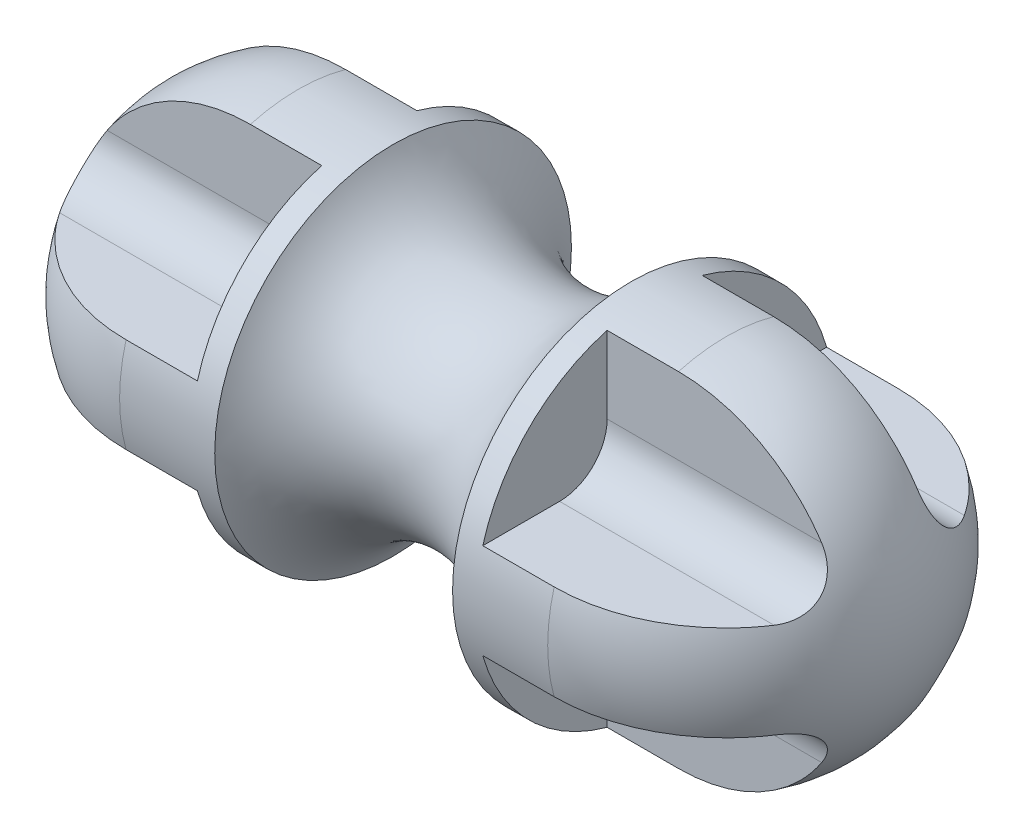
SolidWorks part; units mm, degrees
ref_plane "前视基准面" through (0, 0, 0) normal (0, 0, 1) x (1, 0, 0)
ref_plane "上视基准面" through (0, 0, 0) normal (0, 1, 0) x (1, 0, 0)
ref_plane "右视基准面" through (0, 0, 0) normal (1, 0, 0) x (0, 0, -1)
other "Configuration Table"
sketch "草图1" plane through (0, 0, 0) normal (0, 0, 1) x (1, 0, 0)
  line L0 (0, -37.498) -> (0, 37.498) construction
  line L1 (25, -37.498) -> (25, 37.498)
  line L2 (0, 0) -> (25, 0) construction
  line L3 (0, 22.498) -> (0, -22.498)
  line L4 (0, 0) -> (82.498, 0)
  line L5 (25, 37.498) -> (45, 37.498)
  line L6 (25, 37.498) -> (25, -37.498)
  line L7 (25, -37.498) -> (45, -37.498)
  line L8 (45, 37.498) -> (45, -37.498)
  line L9 (82.498, 0) -> (121.3982, 0) construction
  arc A0 (25, 37.498) -> (0, 22.498) centre (0, 50.8313) cw
  arc A1 (25, -37.498) -> (0, -22.498) centre (0, -50.8313) ccw
  arc A2 (45, 37.498) -> (45, -37.498) centre (45, 0) cw
  point P5 (0, 0)
  point P7 (25, 0)
  dimension "D1" = 25
  dimension "D2" = 74.996
  dimension "D3" = 15
  dimension "D4" = 45
revolve "旋转3" add sketch "草图1" angle 360 about L9 region at (13.5662, 13.7315, 0) region at (35, 18.749, 0) region at (60.9146, 15.9146, 0)
sketch "草图2" plane through (0, 0, 0) normal (-1, 0, 0) x (0, 0, 1)
  line L0 (-10, 36.14) -> (-10, 20)
  line L1 (-20, 10) -> (-36.14, 10)
  line L2 (36.14, 10) -> (20, 10)
  line L3 (10, 20) -> (10, 36.14)
  line L4 (10, -36.14) -> (10, -20)
  line L5 (20, -10) -> (36.14, -10)
  line L6 (-36.14, -10) -> (-20, -10)
  line L7 (-10, -20) -> (-10, -36.14)
  circle A0 centre (0, 0) radius 37.498 construction
  arc A1 (-10, 20) -> (-20, 10) centre (-20, 20) cw
  arc A2 (20, 10) -> (10, 20) centre (20, 20) cw
  circle A3 centre (0, 0) radius 37.498
  arc A4 (-36.14, -10) -> (-10, -36.14) centre (0, 0) ccw
  arc A5 (10, -20) -> (20, -10) centre (20, -20) cw
  arc A6 (-20, -10) -> (-10, -20) centre (-20, -20) cw
  arc A7 (36.14, 10) -> (10, 36.14) centre (0, 0) ccw
  arc A8 (10, -36.14) -> (36.14, -10) centre (0, 0) ccw
  arc A9 (-10, 36.14) -> (-36.14, 10) centre (0, 0) ccw
  dimension "D1" = 10
  dimension "D4" = 20
  dimension "D2" = 0
  dimension "D3" = 4
extrude "切除-拉伸1" cut sketch "草图2" along normal blind 52.5 from offset 82.5 offset against normal yes
mirror "镜向1" about plane through (0, 0, 0) normal (1, 0, 0) of "旋转3", "切除-拉伸1"
